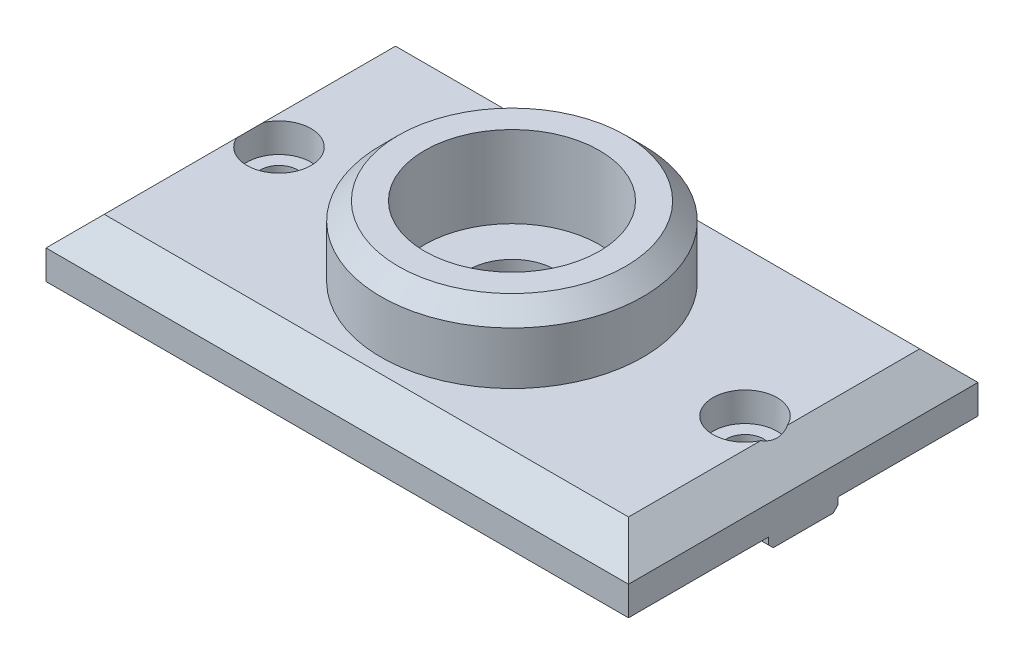
SolidWorks part; units mm, degrees
ref_plane "Płaszczyzna przednia" through (0, 0, 0) normal (0, 0, 1) x (1, 0, 0)
ref_plane "Płaszczyzna górna" through (0, 0, 0) normal (0, 1, 0) x (1, 0, 0)
ref_plane "Płaszczyzna prawa" through (0, 0, 0) normal (1, 0, 0) x (0, 0, -1)
sketch "Sketch1" plane through (0, 0, 0) normal (0, 1, 0) x (1, 0, 0)
  line L1 (-50, -30) -> (50, -30)
  line L2 (-50, -30) -> (-50, 30)
  line L3 (-50, 30) -> (50, 30)
  line L4 (50, -30) -> (50, 30)
  line L5 (-50, -30) -> (50, 30) construction
  line L6 (-50, 30) -> (50, -30) construction
  point P0 (0, 0)
  dimension "D2" = 100
  dimension "D3" = 60
extrude "Boss-Extrude1" add sketch "Sketch1" along normal blind 10
sketch "Sketch3" plane through (0, 0, 0) normal (0, 1, 0) x (1, 0, 0)
  circle A0 centre (0, 0) radius 22.5
  dimension "D1" = 45
extrude "Boss-Extrude2" add sketch "Sketch3" along normal blind 12 from surface starting at face at (0, 10, 0)
sketch "Sketch4" plane through (0, 0, 0) normal (0, 1, 0) x (1, 0, 0)
  circle A0 centre (0, 0) radius 15
  dimension "D1" = 30
extrude "Cut-Extrude2" cut sketch "Sketch4" against normal blind 14 from surface starting at face at (0, 22, -22.5)
sketch "Sketch6" plane through (0, 0, 0) normal (0, 1, 0) x (1, 0, 0)
  line L4 (50, 5.95) -> (50, -5.95)
  line L5 (50, 5.95) -> (-50, 5.95)
  line L7 (50, -5.95) -> (-50, -5.95)
  line L8 (-50, 5.95) -> (-50, -5.95)
  line L9 (50, -30) -> (50, 30) construction
  line L11 (-50, 30) -> (-50, -30) construction
  point P9 (0, 0)
  dimension "D1" = 5.95
  dimension "D2" = 11.9
extrude "Boss-Extrude3" add sketch "Sketch6" against normal blind 2
sketch "Sketch2" plane through (0, 0, 0) normal (0, 1, 0) x (1, 0, 0)
  line L0 (-50, 0) -> (50, 0) construction
  line L1 (-50, 30) -> (-50, -30) construction
  line L2 (50, -30) -> (50, 30) construction
  circle A0 centre (-40, 0) radius 3.2
  circle A1 centre (40, 0) radius 3.2
  dimension "D1" = 6.4
  dimension "D2" = 80
  dimension "D3" = 40
extrude "Cut-Extrude1" cut sketch "Sketch2" along normal through all both and the other way through all
sketch "Sketch5" plane through (0, 0, 0) normal (0, 1, 0) x (1, 0, 0)
  circle A0 centre (0, 0) radius 7.5
  dimension "D1" = 15
extrude "Cut-Extrude3" cut sketch "Sketch5" along normal through all both and the other way through all
sketch "Sketch8" plane through (0, 0, 0) normal (0, 1, 0) x (1, 0, 0)
  circle A0 centre (40, 0) radius 5.5
  circle A1 centre (-40, 0) radius 5.5
  dimension "D1" = 11
extrude "Cut-Extrude4" cut sketch "Sketch8" against normal blind 5 from surface starting at face at (-40, 10, -3.2)
chamfer "Chamfer1" distance 5 angle 45 4 edges at (0, 10, 30) (-50, 10, 0) (0, 10, -30) (50, 10, 0)
chamfer "Chamfer2" distance 3 angle 45 1 edges at (0, 22, -22.5)
chamfer "Chamfer3" distance 0.8 angle 45 4 edges at (-27.283, -2, 5.95) (27.283, -2, 5.95) (-27.283, -2, -5.95) (27.283, -2, -5.95)
